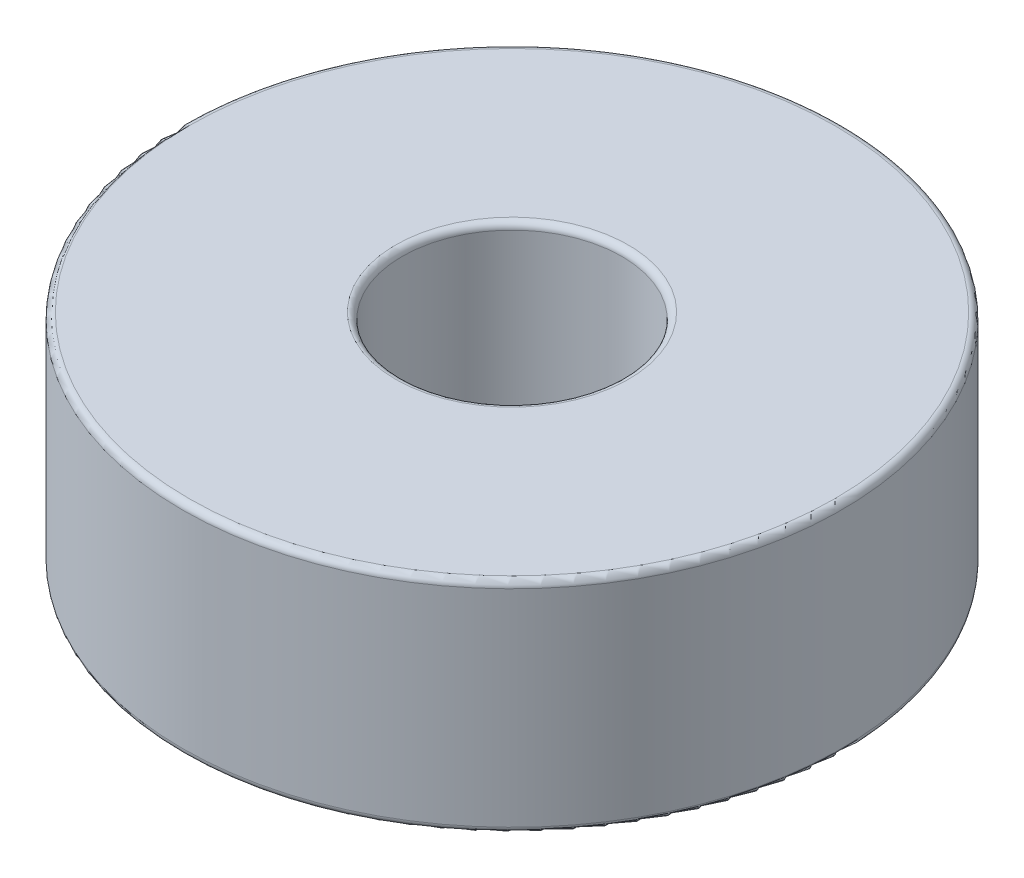
SolidWorks part; units mm, degrees
ref_plane "Front Plane" through (0, 0, 0) normal (0, 0, 1) x (1, 0, 0)
ref_plane "Top Plane" through (0, 0, 0) normal (0, 1, 0) x (1, 0, 0)
ref_plane "Right Plane" through (0, 0, 0) normal (1, 0, 0) x (0, 0, -1)
sketch "Sketch1" plane through (0, 0, 0) normal (0, 1, 0) x (1, 0, 0)
  circle A0 centre (0, 0) radius 15
  dimension "D1" = 30
extrude "Boss-Extrude1" add sketch "Sketch1" along normal blind 10
sketch "Sketch2" plane through (0, 10, 0) normal (0, 1, 0) x (1, 0, 0)
  circle A0 centre (0, 0) radius 5
  point P3 (4.1928, 1.9774)
  point P4 (0, 0)
  dimension "D1" = 10
extrude "Cut-Extrude1" cut sketch "Sketch2" against normal through all both and the other way through all
fillet "Fillet1" radius 0.3 4 edges at (0, 0, 15) (0, 0, 5) (0, 10, 15) (0, 10, 5)
